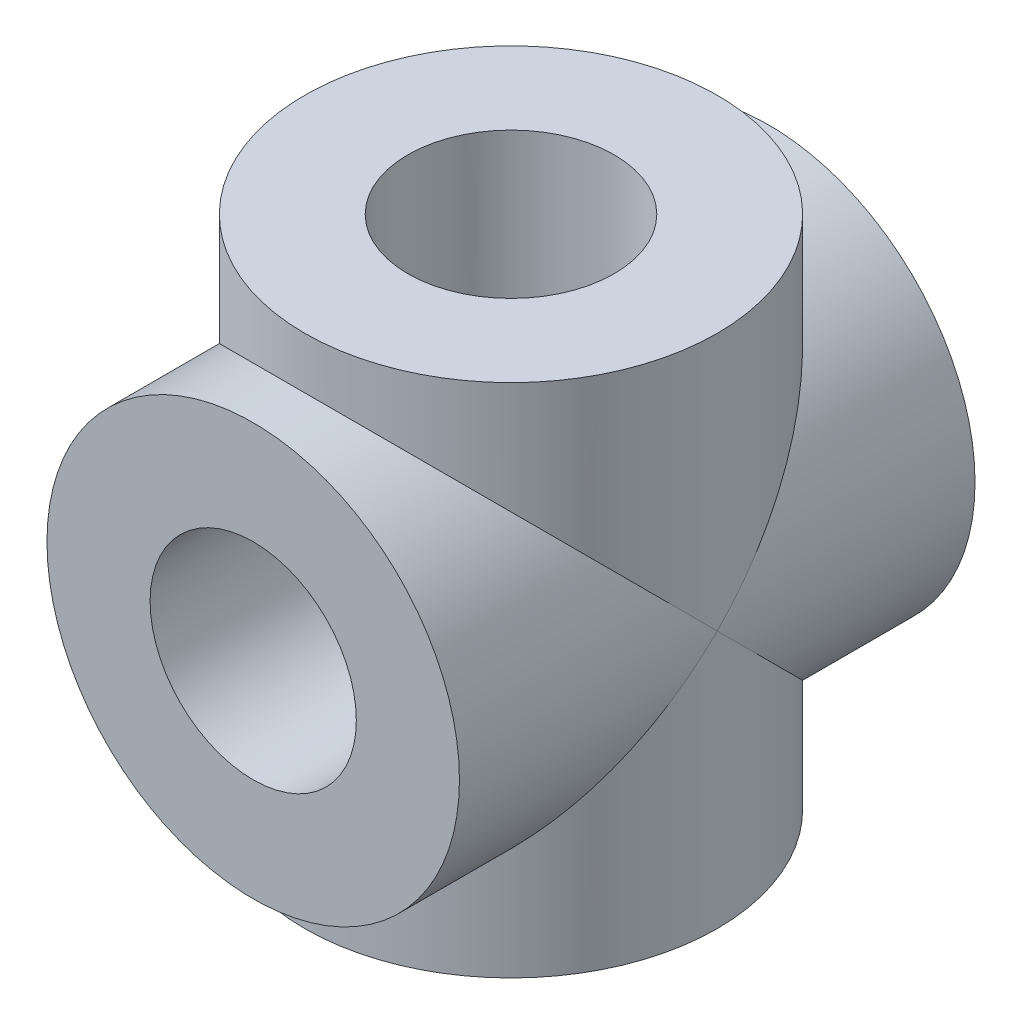
SolidWorks part; units mm, degrees
ref_plane "Front Plane" through (0, 0, 0) normal (0, 0, 1) x (1, 0, 0)
ref_plane "Top Plane" through (0, 0, 0) normal (0, 1, 0) x (1, 0, 0)
ref_plane "Right Plane" through (0, 0, 0) normal (1, 0, 0) x (0, 0, -1)
sketch "Sketch1" plane through (0, 0, 0) normal (0, 0, 1) x (1, 0, 0)
  circle A0 centre (0, 0) radius 2
  circle A1 centre (0, 0) radius 4
  dimension "D1" = 4
  dimension "D2" = 8
extrude "Boss-Extrude1" add sketch "Sketch1" along normal mid plane 10
sketch "Sketch2" plane through (0, 0, 0) normal (0, 1, 0) x (1, 0, 0)
  circle A0 centre (0, 0) radius 4
  circle A1 centre (0, 0) radius 2
  dimension "D1" = 8
  dimension "D2" = 4
extrude "Boss-Extrude2" add sketch "Sketch2" along normal mid plane 10
extrude "Cut-Extrude1" cut sketch "Sketch1<2>" against normal through all both and the other way through all contours A0 region at (0, 0, 0)
sketch "Sketch1<2>" plane through (0, 0, 0) normal (0, 0, 1) x (1, 0, 0) same geometry as "Sketch1"
extrude "Cut-Extrude2" cut sketch "Sketch2<2>" against normal through all both and the other way through all contours A1
sketch "Sketch2<2>" plane through (0, 0, 0) normal (0, 1, 0) x (1, 0, 0) same geometry as "Sketch2"
